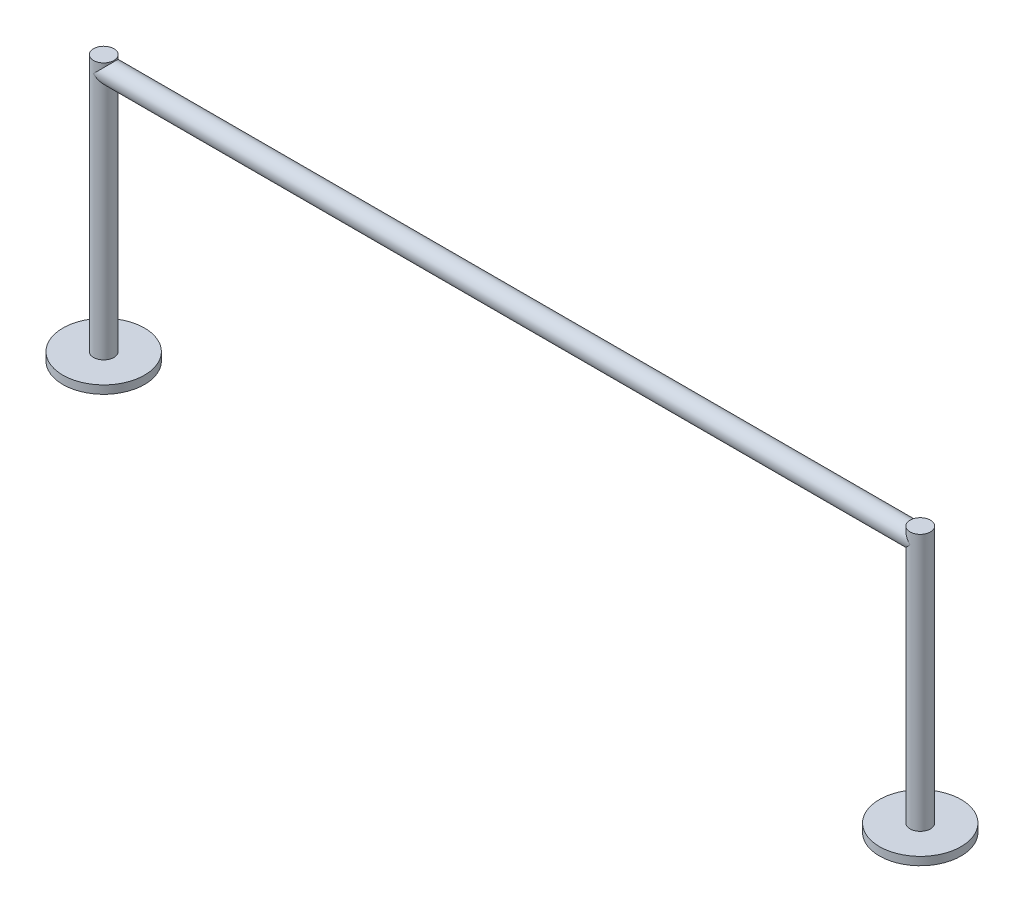
SolidWorks part; units mm, degrees
ref_plane "前视基准面" through (0, 0, 0) normal (0, 0, 1) x (1, 0, 0)
ref_plane "上视基准面" through (0, 0, 0) normal (0, 1, 0) x (1, 0, 0)
ref_plane "右视基准面" through (0, 0, 0) normal (1, 0, 0) x (0, 0, -1)
sketch "草图1" plane through (0, 0, 0) normal (0, 1, 0) x (1, 0, 0)
  line L0 (0, 0) -> (-50000, 0) construction
  circle A0 centre (0, 0) radius 50
  circle A1 centre (1000, 0) radius 50
  point P5 (711.0536, 0)
  dimension "D1" = 100
  dimension "D2" = 100
  dimension "D3" = 1000
extrude "凸台-拉伸1" add sketch "草图1" along normal blind 10
sketch "草图2" plane through (0, 10, 0) normal (0, 1, 0) x (1, 0, 0)
  circle A0 centre (0, 0) radius 2.5
  circle A1 centre (1000, 0) radius 12.5
  circle A2 centre (0, 0) radius 1.25
  circle A3 centre (0, 0) radius 12.5
  dimension "D1" = 25
  dimension "D2" = 25
extrude "凸台-拉伸2" add sketch "草图2" along normal blind 315 contours A1 | A3 region at (1000, 10, 0)
sketch "草图3" plane through (0, 0, 0) normal (1, 0, 0) x (0, 0, -1)
  circle A0 centre (0, 311.1328) radius 12.5
  dimension "D1" = 25
extrude "凸台-拉伸3" add sketch "草图3" along normal blind 1000
